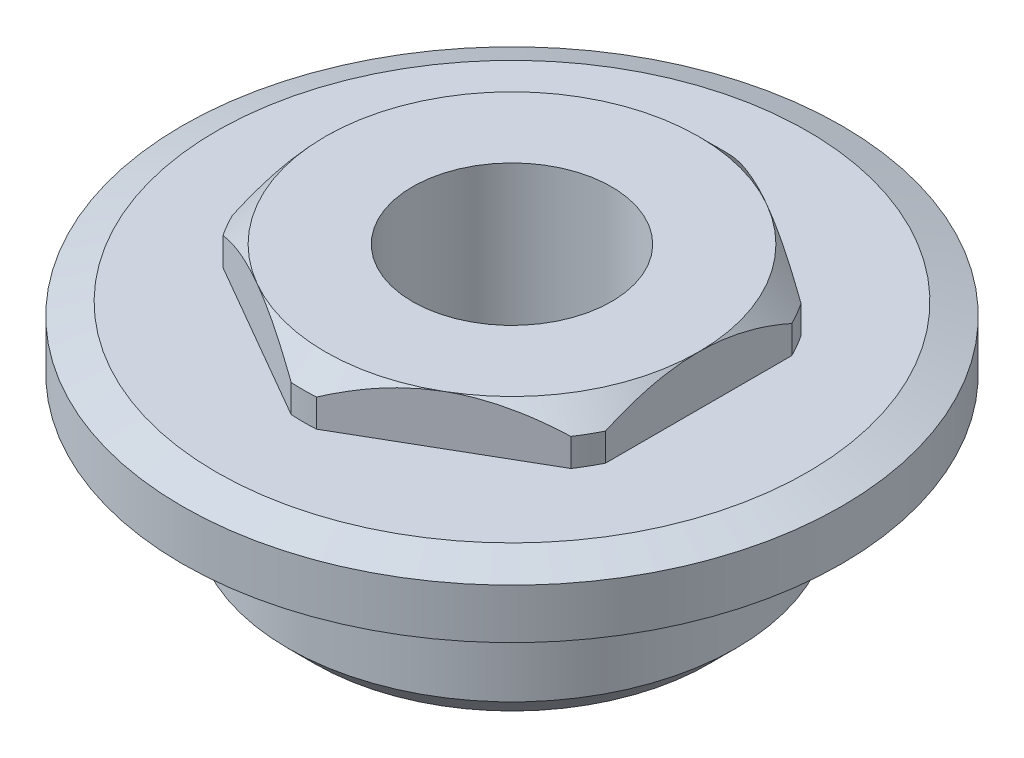
SolidWorks part; units mm, degrees
ref_plane "前视基准面" through (0, 0, 0) normal (0, 0, 1) x (1, 0, 0)
ref_plane "上视基准面" through (0, 0, 0) normal (0, 1, 0) x (1, 0, 0)
ref_plane "右视基准面" through (0, 0, 0) normal (1, 0, 0) x (0, 0, -1)
sketch "草图1" plane through (0, 0, 0) normal (0, 0, 1) x (1, 0, 0)
  line L0 (8, 21.3) -> (8, 10)
  line L1 (8, 10) -> (12.5, 10)
  line L2 (12.5, 10) -> (12.5, 0)
  line L3 (12.5, 0) -> (15.835, 0)
  line L4 (15.835, 0) -> (18, 2.165)
  line L5 (18, 2.165) -> (18, 12.3)
  line L6 (18, 12.3) -> (26.5, 12.3)
  line L7 (26.5, 12.3) -> (26.5, 16.3)
  line L8 (26.5, 16.3) -> (23.7525, 17.3)
  line L9 (23.7525, 17.3) -> (16.765, 17.3)
  line L10 (16.765, 17.3) -> (16.765, 19.535)
  line L11 (16.765, 19.535) -> (15, 21.3)
  line L12 (15, 21.3) -> (8, 21.3)
  line L13 (0, 0) -> (0, 21.3) construction
revolve "旋转1" add sketch "草图1" angle 360 about L13 reverse direction yes
cosmetic thread "装饰螺纹线1" parameters "D1"=8.5501, "D2"=31.67
ref_plane "基准面4" through (0, 21.3, 0) normal (0, 1, 0) x (1, 0, 0)
sketch "草图2" plane through (0, 21.3, 0) normal (0, 1, 0) x (1, 0, 0)
  line L0 (-48.1339, -48.0274) -> (54.3103, -48.0274)
  line L1 (54.3103, -48.0274) -> (54.3103, 47.8144)
  line L2 (54.3103, 47.8144) -> (-48.1339, 47.8144)
  line L3 (-48.1339, 47.8144) -> (-48.1339, -48.0274)
  line L4 (-15, 8.6603) -> (-15, -8.6603)
  line L5 (-15, -8.6603) -> (0, -17.3205)
  line L6 (0, -17.3205) -> (15, -8.6603)
  line L7 (15, -8.6603) -> (15, 8.6603)
  line L8 (15, 8.6603) -> (0, 17.3205)
  line L9 (0, 17.3205) -> (-15, 8.6603)
extrude "切除-拉伸1" cut sketch "草图2" against normal blind 4
ref_plane "piston_to_nut XY" through (0, 0, 0) normal (0, 1, 0) x (1, 0, 0)
ref_plane "piston_to_nut XZ" through (0, 0, 0) normal (0, 0, 1) x (1, 0, 0)
ref_plane "piston_to_nut YZ" through (0, 0, 0) normal (1, 0, 0) x (0, 0, -1)
ref_axis "piston_to_nut X" through (-80.9, 0, 0) along (1, 0, 0)
ref_axis "piston_to_nut Y" through (0, 0, 50) along (0, 0, -1)
ref_axis "piston_to_nut Z" through (0, 50, 0) along (0, -1, 0)
sketch3d "piston_to_nut"
  point P0 (0, 0, 0)
